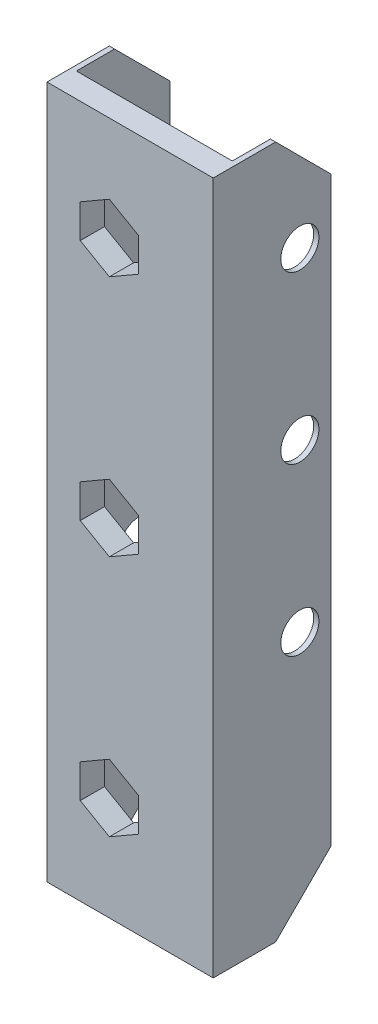
SolidWorks part; units mm, degrees
ref_plane "Front" through (0, 0, 0) normal (0, 0, 1) x (1, 0, 0)
ref_plane "Top" through (0, 0, 0) normal (0, 1, 0) x (1, 0, 0)
ref_plane "Right" through (0, 0, 0) normal (1, 0, 0) x (0, 0, -1)
sketch "Sketch1" plane through (0, 0, 0) normal (0, 1, 0) x (1, 0, 0)
  line L0 (0, 0) -> (0, 17)
  line L1 (0, 17) -> (0.75, 17)
  line L2 (0.75, 17) -> (0.75, 3.5)
  line L3 (0.75, 3.5) -> (23.25, 3.5)
  line L4 (23.25, 3.5) -> (23.25, 17)
  line L5 (23.25, 17) -> (24, 17)
  line L6 (24, 17) -> (24, 0)
  line L7 (24, 0) -> (0, 0)
  dimension "D1" = 3.5
  dimension "D2" = 0.75
  dimension "D3" = 24
  dimension "D4" = 17
extrude "Boss-Extrude1" add sketch "Sketch1" along normal blind 100 contours L3 L4 L5 L6 L7 L0 L1 L2
sketch "Sketch2" plane through (0, 0, 0) normal (0, 0, 1) x (1, 0, 0)
  line L0 (24, 100) -> (0, 100) construction
  line L1 (9, 80.1503) -> (13.2, 82.5751)
  line L2 (13.2, 82.5751) -> (13.2, 87.4249)
  line L3 (13.2, 87.4249) -> (9, 89.8497)
  line L4 (9, 89.8497) -> (4.8, 87.4249)
  line L5 (4.8, 87.4249) -> (4.8, 82.5751)
  line L6 (4.8, 82.5751) -> (9, 80.1503)
  line L7 (9, 45.1503) -> (13.2, 47.5751)
  line L8 (13.2, 47.5751) -> (13.2, 52.4249)
  line L9 (13.2, 52.4249) -> (9, 54.8497)
  line L10 (9, 54.8497) -> (4.8, 52.4249)
  line L11 (4.8, 52.4249) -> (4.8, 47.5751)
  line L12 (4.8, 47.5751) -> (9, 45.1503)
  line L13 (9, 19.8497) -> (4.8, 17.4249)
  line L14 (4.8, 17.4249) -> (4.8, 12.5751)
  line L15 (4.8, 12.5751) -> (9, 10.1503)
  line L16 (9, 10.1503) -> (13.2, 12.5751)
  line L17 (13.2, 12.5751) -> (13.2, 17.4249)
  line L18 (13.2, 17.4249) -> (9, 19.8497)
  line L20 (0, 100) -> (0, 0) construction
  circle A0 centre (9, 85) radius 4.2 construction
  circle A1 centre (9, 50) radius 4.2 construction
  circle A2 centre (9, 15) radius 4.2 construction
  dimension "D1" = 35
  dimension "D2" = 35
  dimension "D3" = 15
  dimension "D4" = 8.4
  dimension "D5" = 9
extrude "Cut-Extrude1" cut sketch "Sketch2" against normal through all both and the other way through all contours L11 L12 L7 L8 L9 L10 | L17 L18 L13 L14 L15 L16 | L5 L6 L1 L2 L3 L4 region at (9, 85, 0) region at (9, 50, 0) region at (9, 15, 0)
hole_wizard "M5 Clearance Hole1" positions "Sketch3" profile "Sketch4" hole size "M5" standard "ISO" end condition through all
sketch "Sketch3" plane through (24, 0, 0) normal (1, 0, 0) x (0, 0, -1)
  line L0 (17, 100) -> (0, 100) construction
  line L2 (3.5, 100) -> (3.5, 0) construction
  point P0 (12.5, 85)
  point P2 (12.5, 37)
  point P4 (12.5, 61)
  dimension "D1" = 24
  dimension "D2" = 24
  dimension "D3" = 15
  dimension "D4" = 9
sketch "Sketch4" plane through (24, 85, -12.5) normal (0, 1, 0) x (0, 0, -1)
  line L0 (0, 0) -> (0, 24)
  line L1 (0, 24) -> (2.75, 24)
  line L2 (2.75, 24) -> (2.75, 0)
  line L5 (2.75, 0) -> (0, 0)
  line L11 (0, -6.35) -> (0, 107.95) construction
  dimension "Thru Hole Dia." = 5.5
  dimension "Thru Hole Depth" = 24
chamfer "Chamfer1" distance 8 angle 45 4 edges at (0.375, 100, -17) (23.625, 100, -17) (23.625, 0, -17) (0.375, 0, -17)
